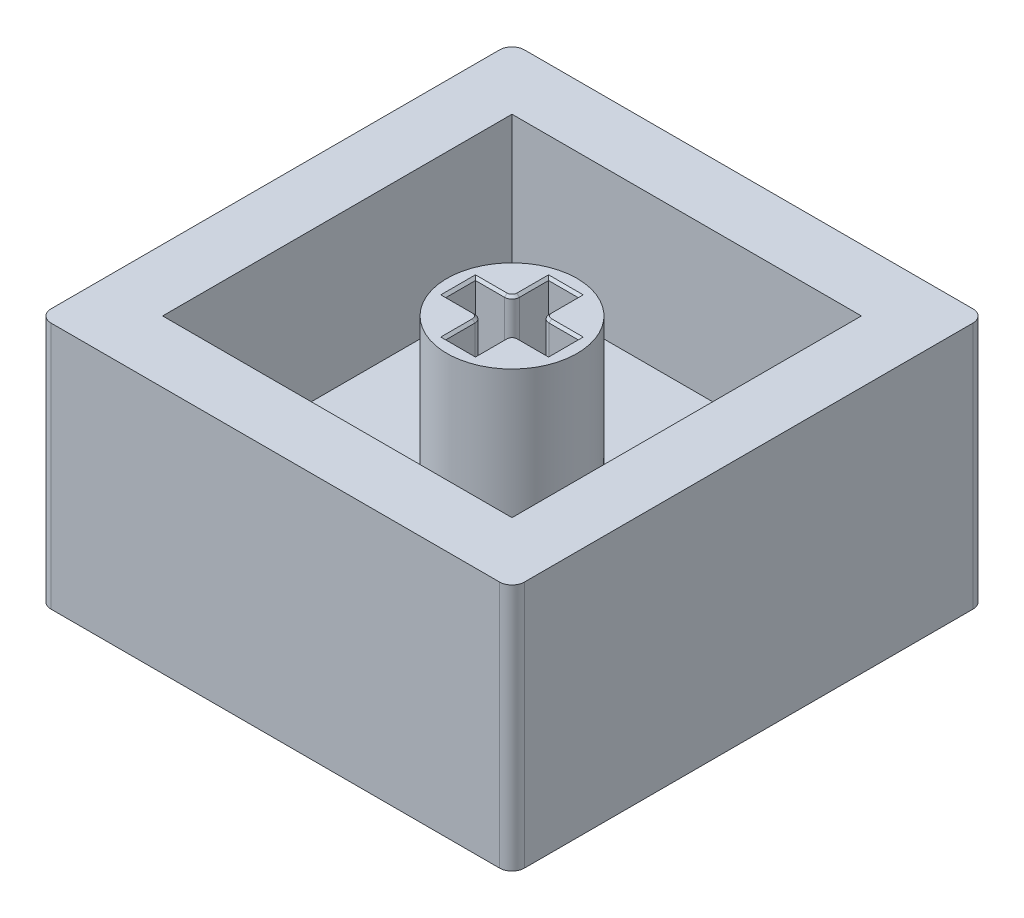
SolidWorks part; units mm, degrees
ref_plane "Front Plane" through (0, 0, 0) normal (0, 0, 1) x (1, 0, 0)
ref_plane "Top Plane" through (0, 0, 0) normal (0, 1, 0) x (1, 0, 0)
ref_plane "Right Plane" through (0, 0, 0) normal (1, 0, 0) x (0, 0, -1)
sketch "Sketch1" plane through (0, 0, 0) normal (0, 1, 0) x (1, 0, 0)
  line L0 (-2.5, -2.5) -> (-2.5, 16.6)
  line L1 (0, 0) -> (14.1, 0)
  line L2 (0, 0) -> (0, 14.1)
  line L3 (0, 14.1) -> (14.1, 14.1)
  line L4 (14.1, 0) -> (14.1, 14.1)
  line L5 (-2.5, 16.6) -> (16.6, 16.6)
  line L6 (16.6, -2.5) -> (16.6, 16.6)
  line L7 (-2.5, -2.5) -> (16.6, -2.5)
  dimension "D2" = 14.1
  dimension "D1" = 2.5
extrude "Boss-Extrude1" add sketch "Sketch1" along normal blind 4 contours L1 L4 L3 L2 | L0 L7 L6 L5 L4 L1 L2 L3 region at (-2.2299, 0, -7.05) region at (7.05, 0, -7.05)
extrude "Boss-Extrude2" add sketch "Sketch1<3>" along normal blind 10
sketch "Sketch1<3>" plane through (0, 0, 0) normal (0, 1, 0) x (1, 0, 0) same geometry as "Sketch1"
sketch "Sketch2" plane through (0, 4, 0) normal (0, 1, 0) x (1, 0, 0)
  line L0 (0, 7.05) -> (14.1, 7.05) construction
  line L1 (0, 0) -> (0, 14.1) construction
  line L2 (14.1, 0) -> (14.1, 14.1) construction
  line L4 (14.1, 14.1) -> (0, 14.1) construction
  line L5 (7.05, 14.1) -> (7.05, 0) construction
  line L6 (14.1, 0) -> (0, 0) construction
  line L7 (4.975, 6.45) -> (9.125, 6.45)
  line L8 (4.975, 6.45) -> (4.975, 7.65)
  line L9 (4.975, 7.65) -> (9.125, 7.65)
  line L10 (9.125, 6.45) -> (9.125, 7.65)
  line L11 (4.975, 6.45) -> (9.125, 7.65) construction
  line L12 (4.975, 7.65) -> (9.125, 6.45) construction
  line L13 (7.65, 4.975) -> (6.45, 4.975)
  line L14 (7.65, 4.975) -> (7.65, 9.125)
  line L15 (7.65, 9.125) -> (6.45, 9.125)
  line L16 (6.45, 4.975) -> (6.45, 9.125)
  line L17 (7.65, 4.975) -> (6.45, 9.125) construction
  line L18 (7.65, 9.125) -> (6.45, 4.975) construction
  line L19 (6.15, 6.15) -> (7.95, 6.15) construction
  line L20 (6.15, 6.15) -> (6.15, 7.95) construction
  line L21 (6.15, 7.95) -> (7.95, 7.95) construction
  line L22 (7.95, 6.15) -> (7.95, 7.95) construction
  line L23 (6.15, 6.15) -> (7.95, 7.95) construction
  line L24 (6.15, 7.95) -> (7.95, 6.15) construction
  circle A0 centre (7.05, 7.05) radius 2.625
  arc A1 (6.15, 7.65) -> (6.45, 7.95) centre (6.15, 7.95) ccw
  arc A2 (7.65, 7.95) -> (7.95, 7.65) centre (7.95, 7.95) ccw
  arc A3 (7.95, 6.45) -> (7.65, 6.15) centre (7.95, 6.15) ccw
  arc A4 (6.45, 6.15) -> (6.15, 6.45) centre (6.15, 6.15) ccw
  dimension "D3" = 0.3
  dimension "D4" = 5.25
  dimension "D1" = 1.2
  dimension "D2" = 4.15
extrude "Boss-Extrude3" add sketch "Sketch2" along normal up to surface (6 mm away) contours A0 L16 A4 L7 L8 L9 A1 L15 L14 A2 L10 A3 L13 region at (4.4992, 4, -7.05) up to face at (7.05, 10, -7.05)
chamfer "Chamfer1" distance 0.1 angle 45 16 edges at (7.7379, 10, -7.7379) (7.65, 10, -8.5375) (7.05, 10, -9.125) (6.45, 10, -8.5375) (6.3621, 10, -7.7379) (8.5375, 10, -7.65) (9.125, 10, -7.05) (8.5375, 10, -6.45) (7.7379, 10, -6.3621) (7.65, 10, -5.5625) (7.05, 10, -4.975) (6.45, 10, -5.5625) (6.3621, 10, -6.3621) (5.5625, 10, -6.45) (4.975, 10, -7.05) (5.5625, 10, -7.65)
fillet "Fillet1" radius 0.5 4 edges at (16.6, 5, -16.6) (16.6, 5, 2.5) (-2.5, 5, 2.5) (-2.5, 5, -16.6)
equation "\"Outer Circle Dia\"= 5.25"
equation "\"Long X Length\"= 4.15"
equation "\"Short X Length\"= 1.2"
equation "\"Fillet Rad\"= 0.3"
equation "\"D3@Sketch2\"=\"Fillet Rad\""
equation "\"D2@Sketch2\"=\"Long X Length\""
equation "\"D4@Sketch2\"=\"Outer Circle Dia\""
equation "\"D1@Sketch2\"=\"Short X Length\""
equation "\"Keycap Height\"= 10"
equation "\"D1@Boss-Extrude2\"=\"Keycap Height\""
equation "\"X Chamfer\"= 0.1"
equation "\"Outer Fillet\"= 0.5"
equation "\"D1@Chamfer1\"=\"X Chamfer\""
equation "\"D1@Fillet1\"=\"Outer Fillet\""
